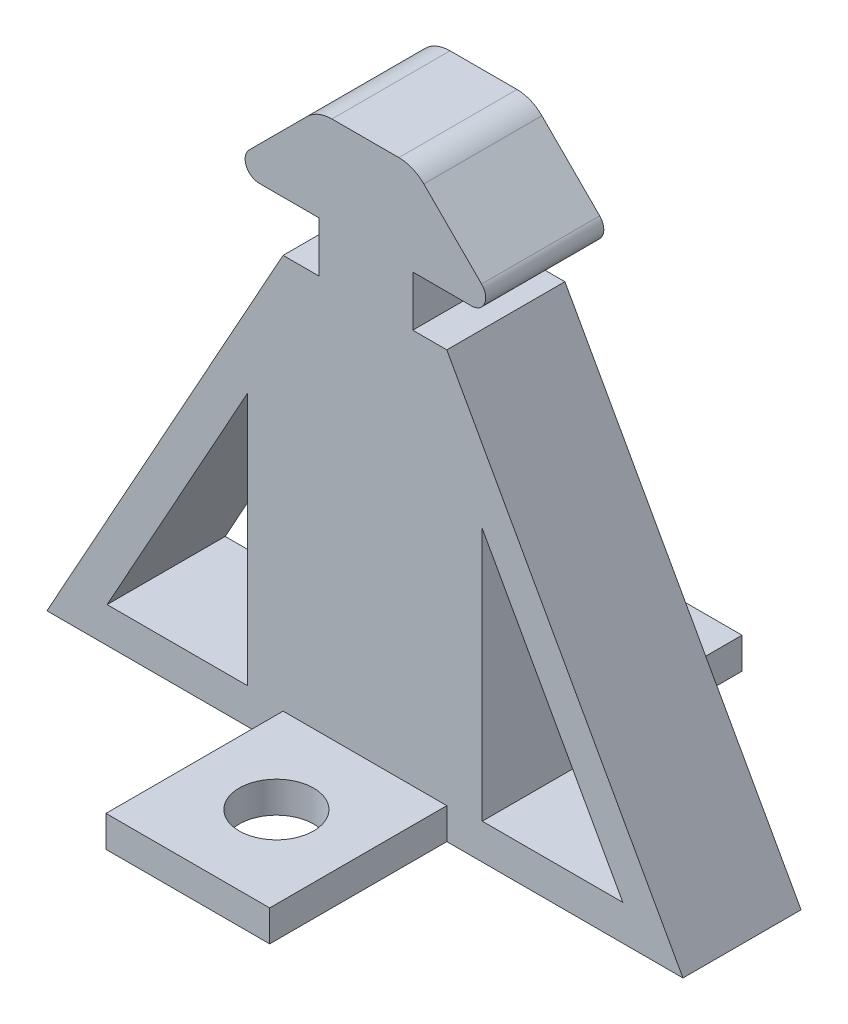
SolidWorks part; units mm, degrees
ref_plane "Front Plane" through (0, 0, 0) normal (0, 0, 1) x (1, 0, 0)
ref_plane "Top Plane" through (0, 0, 0) normal (0, 1, 0) x (1, 0, 0)
ref_plane "Right Plane" through (0, 0, 0) normal (1, 0, 0) x (0, 0, -1)
sketch "Sketch1" plane through (0, 0, 0) normal (0, 0, 1) x (1, 0, 0)
  line L0 (-113.4697, 674.107) -> (-113.4697, 674.0019) construction
  line L1 (-113.4697, 674.0019) -> (-110.4328, 674.0019) construction
  line L2 (-102.4905, 678.271) -> (-97.5028, 678.271)
  line L3 (-113.4697, 674.0019) -> (-110.4328, 674.0019)
  line L4 (-113.4697, 674.0019) -> (-113.4697, 640.5765)
  line L6 (-99.6065, 674.0019) -> (-99.6065, 637.935)
  line L7 (-111.1889, 637.935) -> (-111.1305, 637.935)
  line L8 (-112.2903, 678.271) -> (-110.4328, 678.271)
  line L11 (-110.4328, 678.271) -> (-110.4328, 674.0019)
  line L12 (-111.4436, 685.1974) -> (-116.3373, 680.3036)
  line L13 (-115.4954, 678.271) -> (-112.2903, 678.271)
  line L14 (-96.6608, 680.3036) -> (-101.5546, 685.1974)
  line L15 (-103.6661, 686.072) -> (-109.3321, 686.072)
  line L17 (-102.4905, 678.271) -> (-102.4905, 674.0019)
  line L19 (-102.4905, 674.0019) -> (-99.6065, 674.0019)
  line L20 (-99.6065, 637.935) -> (-113.4697, 637.935)
  line L21 (-111.1889, 637.935) -> (-111.1305, 637.935)
  line L22 (-99.6065, 640.5765) -> (-99.6065, 637.935)
  line L23 (-113.4697, 637.935) -> (-113.4697, 640.5765)
  line L26 (-111.1889, 637.935) -> (-111.1305, 637.935)
  line L27 (-99.6065, 640.5765) -> (-99.6065, 637.935)
  arc A12 (-109.3321, 686.072) -> (-111.4436, 685.1974) centre (-109.3321, 683.0859) ccw
  arc A13 (-116.3373, 680.3036) -> (-115.4954, 678.271) centre (-115.4954, 679.4617) ccw
  arc A14 (-97.5028, 678.271) -> (-96.6608, 680.3036) centre (-97.5028, 679.4617) ccw
  arc A15 (-101.5546, 685.1974) -> (-103.6661, 686.072) centre (-103.6661, 683.0859) ccw
extrude "Boss-Extrude1" add sketch "Sketch1" against normal blind 10 contours L6 L19 L17 L2 A14 L14 A15 L15 A12 L12 A13 L13 L8 L11 L3 L4 L23 L20
sketch "Sketch2" plane through (0, 0, 0) normal (0, 0, 1) x (1, 0, 0)
  line L0 (-113.4697, 674.0019) -> (-113.4697, 637.935) construction
  line L1 (-113.4697, 637.935) -> (-99.6065, 637.935)
  line L2 (-113.4697, 637.935) -> (-113.4697, 640.5756)
  line L3 (-113.4697, 640.5756) -> (-99.6065, 640.5756)
  line L4 (-99.6065, 637.935) -> (-99.6065, 640.5756)
  line L5 (-99.6065, 674.0019) -> (-99.6065, 637.935) construction
  dimension "D1" = 2.6406
extrude "Boss-Extrude2" add sketch "Sketch2" along normal blind 15 and the other way blind 25
sketch "Sketch3" plane through (0, 640.5756, 0) normal (0, 1, 0) x (1, 0, 0)
  line L0 (-106.5381, -15) -> (-106.4991, 0) construction
  line L1 (-99.6065, -15) -> (-113.4697, -15) construction
  line L2 (-103.6661, 0) -> (-109.3321, 0) construction
  line L3 (-99.6065, -7.5) -> (-113.4697, -7.5) construction
  line L4 (-99.6065, -15) -> (-99.6065, 0) construction
  line L5 (-113.4697, -15) -> (-113.4697, 0) construction
  circle A0 centre (-106.5381, -7.5) radius 3.15
extrude "Cut-Extrude1" cut sketch "Sketch3" against normal blind 2.65
sketch "Sketch4" plane through (0, 0, -10) normal (0, 0, -1) x (-1, 0, 0)
  line L0 (99.6065, 637.935) -> (79.6065, 637.935)
  line L1 (79.6065, 637.935) -> (99.6065, 674.0019)
  line L2 (99.6065, 674.0019) -> (99.6065, 637.935)
  line L3 (84.7005, 640.935) -> (96.6065, 662.4057)
  line L4 (96.6065, 662.4057) -> (96.6065, 640.935)
  line L5 (96.6065, 640.935) -> (84.7005, 640.935)
  line L6 (113.4697, 637.935) -> (133.4697, 637.935)
  line L7 (133.4697, 637.935) -> (113.4697, 674.0019)
  line L8 (113.4697, 674.0019) -> (113.4697, 637.935)
  line L9 (116.4697, 662.4057) -> (116.4697, 640.935)
  line L10 (116.4697, 640.935) -> (128.3758, 640.935)
  line L11 (128.3758, 640.935) -> (116.4697, 662.4057)
  point P16 (0, 0)
  dimension "D1" = 41.241
  dimension "D3" = 41.241
  dimension "D2" = 3
  dimension "D4" = 3
extrude "Boss-Extrude3" add sketch "Sketch4" against normal blind 10 contours L5 L4 L3 | L10 L11 L9 | L1 L2 L0 | L7 L8 L6 region at (-92.6378, 648.0919, -10) region at (-120.4384, 648.0919, -10)
sketch "Sketch5" plane through (0, 640.5756, 0) normal (0, 1, 0) x (1, 0, 0)
  line L0 (-106.5381, 25) -> (-106.5381, 10) construction
  line L1 (-99.6065, 25) -> (-113.4697, 25) construction
  line L2 (-99.6065, 10) -> (-113.4697, 10) construction
  line L3 (-106.5381, 10) -> (-113.4697, 17.5) construction
  line L4 (-113.4697, 25) -> (-113.4697, 10) construction
  line L5 (-113.4697, 17.5) -> (-99.6065, 17.5) construction
  line L6 (-99.6065, 25) -> (-99.6065, 10) construction
  circle A0 centre (-106.5381, 17.5) radius 3.15
extrude "Cut-Extrude2" cut sketch "Sketch5" against normal blind 10 contours A0
